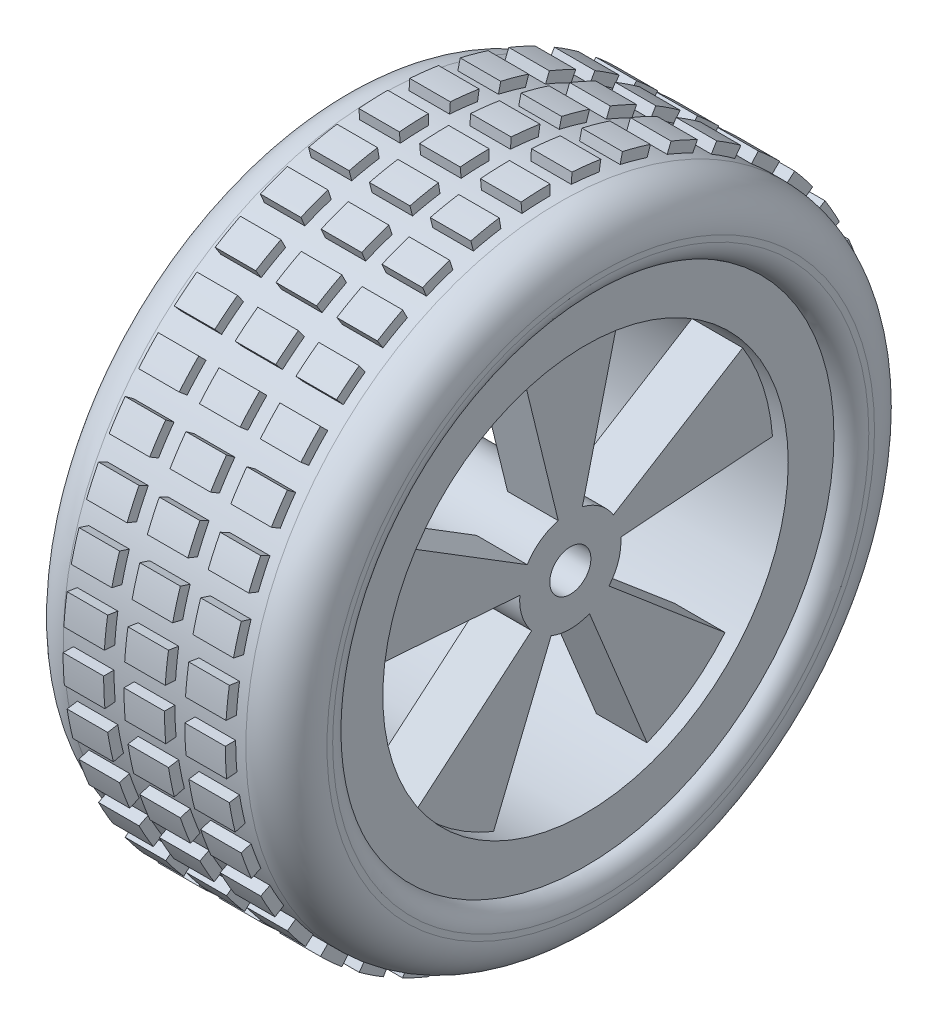
SolidWorks part; units mm, degrees
ref_plane "Front Plane" through (0, 0, 0) normal (0, 0, 1) x (1, 0, 0)
ref_plane "Top Plane" through (0, 0, 0) normal (0, 1, 0) x (1, 0, 0)
ref_plane "Right Plane" through (0, 0, 0) normal (1, 0, 0) x (0, 0, -1)
sketch "Sketch2" plane through (0, 0, 0) normal (1, 0, 0) x (0, 0, -1)
  circle A0 centre (0, 0) radius 31
extrude "Boss-Extrude1" add sketch "Sketch2" along normal blind 13 and the other way blind 13
sketch "Sketch3" plane through (13, 0, 0) normal (1, 0, 0) x (0, 0, -1)
  line L0 (4.981, 0.3706) -> (19.9378, 1.4834)
  line L1 (4.2476, 2.628) -> (17.0019, 10.519)
  line L2 (1.8917, -4.6227) -> (7.5719, -18.5035)
  line L3 (3.8119, -3.2276) -> (15.2581, -12.9192)
  line L4 (-3.8119, -3.2276) -> (-15.2581, -12.9192)
  line L5 (1.1868, 4.8518) -> (4.7503, 19.4203)
  line L6 (-1.1868, 4.8518) -> (-4.7503, 19.4203)
  line L7 (-1.8917, -4.6227) -> (-7.5719, -18.5035)
  line L8 (-4.2476, 2.628) -> (-17.0019, 10.519)
  line L9 (-4.981, 0.3706) -> (-19.9378, 1.4834)
  circle A0 centre (0, 0) radius 4.9948
  circle A1 centre (0, 0) radius 19.9929
  dimension "D1" = 5
extrude "Cut-Extrude1" cut sketch "Sketch3" against normal blind 26 contours L1 A1 L5 A0 | L6 A1 L8 A0 | L9 A1 L4 A0 | L7 A1 L2 A0 | L3 A1 L0 A0 region at (13, -4.2165, -12.9771) region at (13, 11.039, -8.0203) region at (13, -13.6449, 0) region at (13, 11.039, 8.0203) region at (13, -4.2165, 12.9771)
sketch "Sketch4" plane through (13, 0, 0) normal (1, 0, 0) x (0, 0, -1)
  circle A0 centre (0, 0) radius 2.0278
extrude "Cut-Extrude2" cut sketch "Sketch4" against normal blind 26
sketch "Sketch5" plane through (13, 0, 0) normal (1, 0, 0) x (0, 0, -1)
  circle A0 centre (0, 0) radius 19.9929
extrude "Cut-Extrude3" cut sketch "Sketch5" against normal blind 3
sketch "Sketch6" plane through (13, 0, 0) normal (1, 0, 0) x (0, 0, -1)
  circle A0 centre (0, 0) radius 24.5
extrude "Cut-Extrude4" cut sketch "Sketch6" against normal blind 1.5
fillet "Fillet2" radius 4 2 edges at (-13, 0, -31) (13, 0, -31)
fillet "Fillet3" radius 2 1 edges at (13, 0, -24.5)
sketch "Sketch7" plane through (-13, 0, 0) normal (-1, 0, 0) x (0, 0, 1)
  circle A0 centre (0, 0) radius 19.9929
extrude "Cut-Extrude5" cut sketch "Sketch7" against normal blind 18
sketch "Sketch8" plane through (5, 0, 0) normal (-1, 0, 0) x (0, 0, 1)
  circle A0 centre (0, 0) radius 4.9948
  circle A1 centre (0, 0) radius 2.0278
extrude "Boss-Extrude2" add sketch "Sketch8" along normal blind 19
sketch "Sketch9" plane through (0, 0, 0) normal (1, 0, 0) x (0, 0, -1)
  line L0 (0, 31) -> (0, 32.02)
  line L1 (-2.7651, 30.8764) -> (-2.856, 31.8923)
  line L2 (2.0991, 30.9288) -> (2.1682, 31.9465)
  line L3 (4.8495, 30.6183) -> (5.009, 31.6257)
  line L4 (6.9116, 30.2197) -> (7.139, 31.214)
  line L5 (9.5795, 29.4828) -> (9.8947, 30.4528)
  line L6 (11.5539, 28.7664) -> (11.9341, 29.7129)
  line L7 (14.0737, 27.6212) -> (14.5368, 28.53)
  line L8 (15.9117, 26.6048) -> (16.4353, 27.4802)
  line L9 (18.2213, 25.0795) -> (18.8209, 25.9047)
  line L10 (19.8778, 23.7881) -> (20.5318, 24.5708)
  line L11 (21.9203, 21.9203) -> (22.6415, 22.6415)
  line L12 (23.3543, 20.3857) -> (24.1227, 21.0564)
  line L13 (25.0795, 18.2213) -> (25.9047, 18.8209)
  line L14 (26.2558, 16.4813) -> (27.1197, 17.0236)
  line L15 (27.6212, 14.0737) -> (28.53, 14.5368)
  line L16 (28.5108, 12.1711) -> (29.4488, 12.5715)
  line L17 (29.4828, 9.5795) -> (30.4528, 9.8947)
  line L18 (30.0637, 7.5612) -> (31.0529, 7.8099)
  line L19 (30.6183, 4.8495) -> (31.6257, 5.009)
  line L20 (30.8764, 2.7651) -> (31.8923, 2.856)
  line L21 (31, 0) -> (32.02, 0)
  line L22 (30.9288, -2.0991) -> (31.9465, -2.1682)
  line L23 (30.6183, -4.8495) -> (31.6257, -5.009)
  line L24 (30.2197, -6.9116) -> (31.214, -7.139)
  line L25 (29.4828, -9.5795) -> (30.4528, -9.8947)
  line L26 (28.7664, -11.5539) -> (29.7129, -11.9341)
  line L27 (27.6212, -14.0737) -> (28.53, -14.5368)
  line L28 (26.6048, -15.9117) -> (27.4802, -16.4353)
  line L29 (25.0795, -18.2213) -> (25.9047, -18.8209)
  line L30 (23.7881, -19.8778) -> (24.5708, -20.5318)
  line L31 (21.9203, -21.9203) -> (22.6415, -22.6415)
  line L32 (20.3857, -23.3543) -> (21.0564, -24.1227)
  line L33 (18.2213, -25.0795) -> (18.8209, -25.9047)
  line L34 (16.4813, -26.2558) -> (17.0236, -27.1197)
  line L35 (14.0737, -27.6212) -> (14.5368, -28.53)
  line L36 (12.1711, -28.5108) -> (12.5715, -29.4488)
  line L37 (9.5795, -29.4828) -> (9.8947, -30.4528)
  line L38 (7.5612, -30.0637) -> (7.8099, -31.0529)
  line L39 (4.8495, -30.6183) -> (5.009, -31.6257)
  line L40 (2.7651, -30.8764) -> (2.856, -31.8923)
  line L41 (0, -31) -> (0, -32.02)
  line L42 (-2.0991, -30.9288) -> (-2.1682, -31.9465)
  line L43 (-4.8495, -30.6183) -> (-5.009, -31.6257)
  line L44 (-6.9116, -30.2197) -> (-7.139, -31.214)
  line L45 (-9.5795, -29.4828) -> (-9.8947, -30.4528)
  line L46 (-11.5539, -28.7664) -> (-11.9341, -29.7129)
  line L47 (-14.0737, -27.6212) -> (-14.5368, -28.53)
  line L48 (-15.9117, -26.6048) -> (-16.4353, -27.4802)
  line L49 (-18.2213, -25.0795) -> (-18.8209, -25.9047)
  line L50 (-19.8778, -23.7881) -> (-20.5318, -24.5708)
  line L51 (-21.9203, -21.9203) -> (-22.6415, -22.6415)
  line L52 (-23.3543, -20.3857) -> (-24.1227, -21.0564)
  line L53 (-25.0795, -18.2213) -> (-25.9047, -18.8209)
  line L54 (-26.2558, -16.4813) -> (-27.1197, -17.0236)
  line L55 (-27.6212, -14.0737) -> (-28.53, -14.5368)
  line L56 (-28.5108, -12.1711) -> (-29.4488, -12.5715)
  line L57 (-29.4828, -9.5795) -> (-30.4528, -9.8947)
  line L58 (-30.0637, -7.5612) -> (-31.0529, -7.8099)
  line L59 (-30.6183, -4.8495) -> (-31.6257, -5.009)
  line L60 (-30.8764, -2.7651) -> (-31.8923, -2.856)
  line L61 (-31, 0) -> (-32.02, 0)
  line L62 (-30.9288, 2.0991) -> (-31.9465, 2.1682)
  line L63 (-30.6183, 4.8495) -> (-31.6257, 5.009)
  line L64 (-30.2197, 6.9116) -> (-31.214, 7.139)
  line L65 (-29.4828, 9.5795) -> (-30.4528, 9.8947)
  line L66 (-28.7664, 11.5539) -> (-29.7129, 11.9341)
  line L67 (-27.6212, 14.0737) -> (-28.53, 14.5368)
  line L68 (-26.6048, 15.9117) -> (-27.4802, 16.4353)
  line L69 (-25.0795, 18.2213) -> (-25.9047, 18.8209)
  line L70 (-23.7881, 19.8778) -> (-24.5708, 20.5318)
  line L71 (-21.9203, 21.9203) -> (-22.6415, 22.6415)
  line L72 (-20.3857, 23.3543) -> (-21.0564, 24.1227)
  line L73 (-18.2213, 25.0795) -> (-18.8209, 25.9047)
  line L74 (-16.4813, 26.2558) -> (-17.0236, 27.1197)
  line L75 (-14.0737, 27.6212) -> (-14.5368, 28.53)
  line L76 (-12.1711, 28.5108) -> (-12.5715, 29.4488)
  line L77 (-9.5795, 29.4828) -> (-9.8947, 30.4528)
  line L78 (-7.5612, 30.0637) -> (-7.8099, 31.0529)
  line L79 (-4.8495, 30.6183) -> (-5.009, 31.6257)
  arc A0 (0, 32.02) -> (-2.856, 31.8923) centre (0, 0) ccw
  arc A1 (0, 31) -> (-2.7651, 30.8764) centre (0, 0) ccw
  arc A2 (5.009, 31.6257) -> (2.1682, 31.9465) centre (0, 0) ccw
  arc A3 (4.8495, 30.6183) -> (2.0991, 30.9288) centre (0, 0) ccw
  arc A4 (9.8947, 30.4528) -> (7.139, 31.214) centre (0, 0) ccw
  arc A5 (9.5795, 29.4828) -> (6.9116, 30.2197) centre (0, 0) ccw
  arc A6 (14.5368, 28.53) -> (11.9341, 29.7129) centre (0, 0) ccw
  arc A7 (14.0737, 27.6212) -> (11.5539, 28.7664) centre (0, 0) ccw
  arc A8 (18.8209, 25.9047) -> (16.4353, 27.4802) centre (0, 0) ccw
  arc A9 (18.2213, 25.0795) -> (15.9117, 26.6048) centre (0, 0) ccw
  arc A10 (22.6415, 22.6415) -> (20.5318, 24.5708) centre (0, 0) ccw
  arc A11 (21.9203, 21.9203) -> (19.8778, 23.7881) centre (0, 0) ccw
  arc A12 (25.9047, 18.8209) -> (24.1227, 21.0564) centre (0, 0) ccw
  arc A13 (25.0795, 18.2213) -> (23.3543, 20.3857) centre (0, 0) ccw
  arc A14 (28.53, 14.5368) -> (27.1197, 17.0236) centre (0, 0) ccw
  arc A15 (27.6212, 14.0737) -> (26.2558, 16.4813) centre (0, 0) ccw
  arc A16 (30.4528, 9.8947) -> (29.4488, 12.5715) centre (0, 0) ccw
  arc A17 (29.4828, 9.5795) -> (28.5108, 12.1711) centre (0, 0) ccw
  arc A18 (31.6257, 5.009) -> (31.0529, 7.8099) centre (0, 0) ccw
  arc A19 (30.6183, 4.8495) -> (30.0637, 7.5612) centre (0, 0) ccw
  arc A20 (32.02, 0) -> (31.8923, 2.856) centre (0, 0) ccw
  arc A21 (31, 0) -> (30.8764, 2.7651) centre (0, 0) ccw
  arc A22 (31.6257, -5.009) -> (31.9465, -2.1682) centre (0, 0) ccw
  arc A23 (30.6183, -4.8495) -> (30.9288, -2.0991) centre (0, 0) ccw
  arc A24 (30.4528, -9.8947) -> (31.214, -7.139) centre (0, 0) ccw
  arc A25 (29.4828, -9.5795) -> (30.2197, -6.9116) centre (0, 0) ccw
  arc A26 (28.53, -14.5368) -> (29.7129, -11.9341) centre (0, 0) ccw
  arc A27 (27.6212, -14.0737) -> (28.7664, -11.5539) centre (0, 0) ccw
  arc A28 (25.9047, -18.8209) -> (27.4802, -16.4353) centre (0, 0) ccw
  arc A29 (25.0795, -18.2213) -> (26.6048, -15.9117) centre (0, 0) ccw
  arc A30 (22.6415, -22.6415) -> (24.5708, -20.5318) centre (0, 0) ccw
  arc A31 (21.9203, -21.9203) -> (23.7881, -19.8778) centre (0, 0) ccw
  arc A32 (18.8209, -25.9047) -> (21.0564, -24.1227) centre (0, 0) ccw
  arc A33 (18.2213, -25.0795) -> (20.3857, -23.3543) centre (0, 0) ccw
  arc A34 (14.5368, -28.53) -> (17.0236, -27.1197) centre (0, 0) ccw
  arc A35 (14.0737, -27.6212) -> (16.4813, -26.2558) centre (0, 0) ccw
  arc A36 (9.8947, -30.4528) -> (12.5715, -29.4488) centre (0, 0) ccw
  arc A37 (9.5795, -29.4828) -> (12.1711, -28.5108) centre (0, 0) ccw
  arc A38 (5.009, -31.6257) -> (7.8099, -31.0529) centre (0, 0) ccw
  arc A39 (4.8495, -30.6183) -> (7.5612, -30.0637) centre (0, 0) ccw
  arc A40 (0, -32.02) -> (2.856, -31.8923) centre (0, 0) ccw
  arc A41 (0, -31) -> (2.7651, -30.8764) centre (0, 0) ccw
  arc A42 (-5.009, -31.6257) -> (-2.1682, -31.9465) centre (0, 0) ccw
  arc A43 (-4.8495, -30.6183) -> (-2.0991, -30.9288) centre (0, 0) ccw
  arc A44 (-9.8947, -30.4528) -> (-7.139, -31.214) centre (0, 0) ccw
  arc A45 (-9.5795, -29.4828) -> (-6.9116, -30.2197) centre (0, 0) ccw
  arc A46 (-14.5368, -28.53) -> (-11.9341, -29.7129) centre (0, 0) ccw
  arc A47 (-14.0737, -27.6212) -> (-11.5539, -28.7664) centre (0, 0) ccw
  arc A48 (-18.8209, -25.9047) -> (-16.4353, -27.4802) centre (0, 0) ccw
  arc A49 (-18.2213, -25.0795) -> (-15.9117, -26.6048) centre (0, 0) ccw
  arc A50 (-22.6415, -22.6415) -> (-20.5318, -24.5708) centre (0, 0) ccw
  arc A51 (-21.9203, -21.9203) -> (-19.8778, -23.7881) centre (0, 0) ccw
  arc A52 (-25.9047, -18.8209) -> (-24.1227, -21.0564) centre (0, 0) ccw
  arc A53 (-25.0795, -18.2213) -> (-23.3543, -20.3857) centre (0, 0) ccw
  arc A54 (-28.53, -14.5368) -> (-27.1197, -17.0236) centre (0, 0) ccw
  arc A55 (-27.6212, -14.0737) -> (-26.2558, -16.4813) centre (0, 0) ccw
  arc A56 (-30.4528, -9.8947) -> (-29.4488, -12.5715) centre (0, 0) ccw
  arc A57 (-29.4828, -9.5795) -> (-28.5108, -12.1711) centre (0, 0) ccw
  arc A58 (-31.6257, -5.009) -> (-31.0529, -7.8099) centre (0, 0) ccw
  arc A59 (-30.6183, -4.8495) -> (-30.0637, -7.5612) centre (0, 0) ccw
  arc A60 (-32.02, 0) -> (-31.8923, -2.856) centre (0, 0) ccw
  arc A61 (-31, 0) -> (-30.8764, -2.7651) centre (0, 0) ccw
  arc A62 (-31.6257, 5.009) -> (-31.9465, 2.1682) centre (0, 0) ccw
  arc A63 (-30.6183, 4.8495) -> (-30.9288, 2.0991) centre (0, 0) ccw
  arc A64 (-30.4528, 9.8947) -> (-31.214, 7.139) centre (0, 0) ccw
  arc A65 (-29.4828, 9.5795) -> (-30.2197, 6.9116) centre (0, 0) ccw
  arc A66 (-28.53, 14.5368) -> (-29.7129, 11.9341) centre (0, 0) ccw
  arc A67 (-27.6212, 14.0737) -> (-28.7664, 11.5539) centre (0, 0) ccw
  arc A68 (-25.9047, 18.8209) -> (-27.4802, 16.4353) centre (0, 0) ccw
  arc A69 (-25.0795, 18.2213) -> (-26.6048, 15.9117) centre (0, 0) ccw
  arc A70 (-22.6415, 22.6415) -> (-24.5708, 20.5318) centre (0, 0) ccw
  arc A71 (-21.9203, 21.9203) -> (-23.7881, 19.8778) centre (0, 0) ccw
  arc A72 (-18.8209, 25.9047) -> (-21.0564, 24.1227) centre (0, 0) ccw
  arc A73 (-18.2213, 25.0795) -> (-20.3857, 23.3543) centre (0, 0) ccw
  arc A74 (-14.5368, 28.53) -> (-17.0236, 27.1197) centre (0, 0) ccw
  arc A75 (-14.0737, 27.6212) -> (-16.4813, 26.2558) centre (0, 0) ccw
  arc A76 (-9.8947, 30.4528) -> (-12.5715, 29.4488) centre (0, 0) ccw
  arc A77 (-9.5795, 29.4828) -> (-12.1711, 28.5108) centre (0, 0) ccw
  arc A78 (-5.009, 31.6257) -> (-7.8099, 31.0529) centre (0, 0) ccw
  arc A79 (-4.8495, 30.6183) -> (-7.5612, 30.0637) centre (0, 0) ccw
  dimension "D1" = 40
extrude "Boss-Extrude3" add sketch "Sketch9" along normal blind 2 and the other way blind 2
ref_plane "Plane1" through (3, 0, 0) normal (1, 0, 0) x (0, 0, -1)
mirror "Mirror1" about plane through (3, 0, 0) normal (1, 0, 0) of "Boss-Extrude3"
mirror "Mirror2" about plane through (0, 0, 0) normal (1, 0, 0) of "Mirror1"
sketch "Sketch11" plane through (-13, 0, 0) normal (-1, 0, 0) x (0, 0, 1)
  circle A0 centre (0, 0) radius 19.9929
  circle A1 centre (0, 0) radius 24.5
extrude "Cut-Extrude7" cut sketch "Sketch11" against normal blind 1
fillet "Fillet4" radius 1 1 edges at (-13, 0, 24.5)
